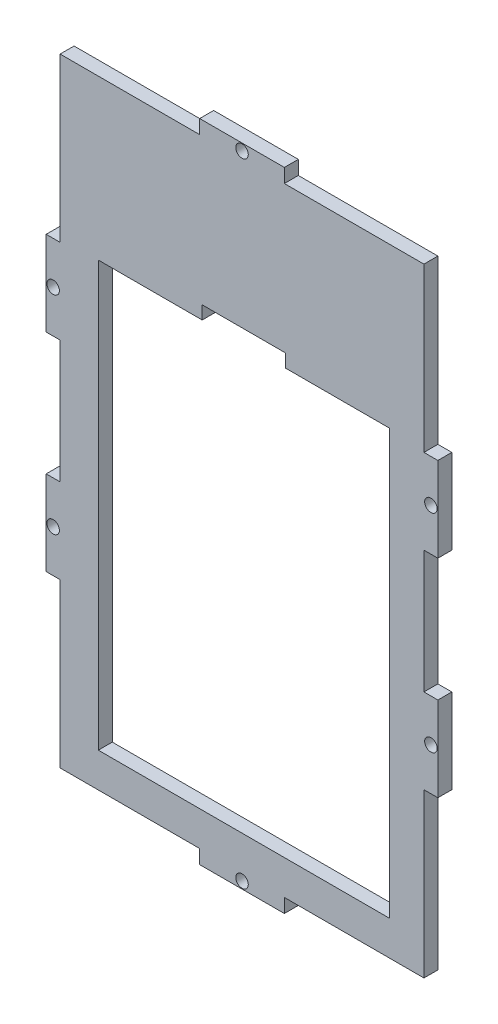
SolidWorks part; units mm, degrees
ref_plane "Front Plane" through (0, 0, 0) normal (0, 0, 1) x (1, 0, 0)
ref_plane "Top Plane" through (0, 0, 0) normal (0, 1, 0) x (1, 0, 0)
ref_plane "Right Plane" through (0, 0, 0) normal (1, 0, 0) x (0, 0, -1)
sketch "Sketch1" plane through (0, 0, 0) normal (0, 0, 1) x (1, 0, 0)
  line L0 (-41.465, 70.465) -> (-13.8217, 70.465)
  line L1 (-41.465, -70.465) -> (41.465, -70.465)
  line L2 (-41.465, -70.465) -> (-41.465, 70.465)
  line L3 (-41.465, 70.465) -> (41.465, 70.465) construction
  line L4 (41.465, -70.465) -> (41.465, 70.465)
  line L5 (-41.465, -70.465) -> (41.465, 70.465) construction
  line L6 (-41.465, 70.465) -> (41.465, -70.465) construction
  line L7 (-13.8217, 70.465) -> (13.8217, 70.465)
  line L8 (13.8217, 70.465) -> (41.465, 70.465)
  point P0 (0, 0)
  dimension "D1" = 82.93
  dimension "D2" = 140.93
extrude "Boss-Extrude1" add sketch "Sketch1" along normal blind 3.18
sketch "Sketch3" plane through (0, 0, 0) normal (0, 0, -1) x (-1, 0, 0)
  line L0 (-33.5967, 34.1533) -> (-33.5967, -62.5967)
  line L1 (-33.5967, -62.5967) -> (32.7533, -62.5967)
  line L2 (32.7533, -62.5967) -> (32.7533, 34.1533)
  line L3 (32.7533, 34.1533) -> (9.0783, 34.1533)
  line L4 (9.0783, 34.1533) -> (9.0783, 37.1533)
  line L5 (9.0783, 37.1533) -> (-9.9217, 37.1533)
  line L6 (-9.9217, 37.1533) -> (-9.9217, 34.1533)
  line L7 (-9.9217, 34.1533) -> (-33.5967, 34.1533)
  line L8 (32.7533, 43.1533) -> (-33.5967, 43.1533)
  line L9 (32.7533, -62.5967) -> (32.7533, 43.1533)
  line L10 (-33.5967, -62.5967) -> (32.7533, -62.5967)
  line L11 (-33.5967, 43.1533) -> (-33.5967, -62.5967)
  line L12 (-33.5967, -62.5967) -> (-33.5967, -70.465) construction
  line L13 (41.465, -70.465) -> (-41.465, -70.465) construction
  line L14 (-33.5967, -62.5967) -> (-41.465, -62.5967) construction
  line L15 (-41.465, -70.465) -> (-41.465, 70.465) construction
  dimension "D1" = 66.35
  dimension "D2" = 96.75
  dimension "D3" = 105.75
  dimension "D4" = 19
  dimension "D5" = 3
extrude "Cut-Extrude1" cut sketch "Sketch3" against normal through all contours L6 L7 L0 L1 L2 L3 L4 L5 region at (0.4217, -13.7828, 0)
sketch "Sketch4" plane through (-41.465, 0, 0) normal (-1, 0, 0) x (0, 0, 1)
  line L0 (1.59, -70.465) -> (1.59, -23.645) construction
  line L1 (3.18, -70.465) -> (0, -70.465) construction
  line L2 (1.59, 70.465) -> (1.59, 23.645) construction
  line L3 (3.18, 70.465) -> (0, 70.465) construction
  line L4 (3.18, 70.465) -> (3.18, -70.465) construction
  line L5 (0, 33.295) -> (3.18, 33.295)
  line L6 (0, 33.295) -> (0, 13.995)
  line L7 (0, 13.995) -> (3.18, 13.995)
  line L8 (3.18, 33.295) -> (3.18, 13.995)
  line L9 (0, 33.295) -> (3.18, 13.995) construction
  line L10 (0, 13.995) -> (3.18, 33.295) construction
  line L12 (0, -33.295) -> (3.18, -33.295)
  line L13 (0, -33.295) -> (0, -13.995)
  line L14 (0, -13.995) -> (3.18, -13.995)
  line L15 (3.18, -33.295) -> (3.18, -13.995)
  line L16 (0, -33.295) -> (3.18, -13.995) construction
  line L17 (0, -13.995) -> (3.18, -33.295) construction
  dimension "D1" = 19.3
  dimension "D2" = 46.82
  dimension "D3" = 46.82
extrude "Boss-Extrude2" add sketch "Sketch4" along normal blind 3.18
sketch "Sketch5" plane through (0, 0, 3.18) normal (0, 0, 1) x (1, 0, 0)
  line L0 (-43.055, 33.295) -> (-43.055, 13.995) construction
  line L1 (-44.645, 33.295) -> (-41.465, 33.295) construction
  line L2 (-44.645, 13.995) -> (-41.465, 13.995) construction
  line L3 (-43.055, -13.995) -> (-43.055, -33.295) construction
  line L4 (-44.645, -13.995) -> (-41.465, -13.995) construction
  line L5 (-44.645, -33.295) -> (-41.465, -33.295) construction
  circle A0 centre (-43.055, 23.645) radius 1.425
  circle A1 centre (-43.055, -23.645) radius 1.425
extrude "Cut-Extrude2" cut sketch "Sketch5" against normal through all
sketch "Sketch6" plane through (41.465, 0, 0) normal (1, 0, 0) x (0, 0, -1)
  line L0 (-1.59, 70.465) -> (-1.59, 23.645) construction
  line L1 (-3.18, 70.465) -> (0, 70.465) construction
  line L2 (-1.59, -70.465) -> (-1.59, -23.645) construction
  line L3 (-3.18, -70.465) -> (0, -70.465) construction
  line L4 (0, -70.465) -> (0, 70.465) construction
  line L5 (-3.18, -33.295) -> (0, -33.295)
  line L6 (-3.18, -33.295) -> (-3.18, -13.995)
  line L7 (-3.18, -13.995) -> (0, -13.995)
  line L8 (0, -33.295) -> (0, -13.995)
  line L9 (-3.18, -33.295) -> (0, -13.995) construction
  line L10 (-3.18, -13.995) -> (0, -33.295) construction
  line L12 (-3.18, 33.295) -> (0, 33.295)
  line L13 (-3.18, 33.295) -> (-3.18, 13.995)
  line L14 (-3.18, 13.995) -> (0, 13.995)
  line L15 (0, 33.295) -> (0, 13.995)
  line L16 (-3.18, 33.295) -> (0, 13.995) construction
  line L17 (-3.18, 13.995) -> (0, 33.295) construction
  dimension "D1" = 19.3
  dimension "D2" = 46.82
  dimension "D3" = 46.82
extrude "Boss-Extrude3" add sketch "Sketch6" along normal blind 3.18
sketch "Sketch7" plane through (0, 0, 3.18) normal (0, 0, 1) x (1, 0, 0)
  line L0 (43.055, 33.295) -> (43.055, 13.995) construction
  line L1 (44.645, 33.295) -> (41.465, 33.295) construction
  line L2 (44.645, 13.995) -> (41.465, 13.995) construction
  line L3 (43.055, -13.995) -> (43.055, -33.295) construction
  line L4 (44.645, -13.995) -> (41.465, -13.995) construction
  line L5 (44.645, -33.295) -> (41.465, -33.295) construction
  circle A0 centre (43.055, 23.645) radius 1.425
  circle A1 centre (43.055, -23.645) radius 1.425
extrude "Cut-Extrude3" cut sketch "Sketch7" against normal through all
sketch "Sketch9" plane through (-41.465, 0, 0) normal (-1, 0, 0) x (0, 0, 1)
  line L0 (0, 51.88) -> (3.18, 51.88) construction
  line L1 (0, 70.465) -> (0, 33.295) construction
  line L2 (3.18, 70.465) -> (3.18, 33.295) construction
  line L4 (0, 42.23) -> (3.18, 42.23)
  line L5 (0, 42.23) -> (0, 61.53)
  line L6 (0, 61.53) -> (3.18, 61.53)
  line L7 (3.18, 42.23) -> (3.18, 61.53)
  line L8 (0, 42.23) -> (3.18, 61.53) construction
  line L9 (0, 61.53) -> (3.18, 42.23) construction
  point P6 (1.59, 51.88)
  dimension "D1" = 19.3
extrude "Boss-Extrude4" [suppressed] add sketch "Sketch9" along normal blind 3.18
sketch "Sketch10" [suppressed] plane through (0, 0, 3.18) normal (0, 0, 1) x (1, 0, 0)
  line L0 (-43.055, 9.65) -> (-43.055, -9.65) construction
  line L1 (-44.645, 9.65) -> (-41.465, 9.65) construction
  line L2 (-44.645, -9.65) -> (-41.465, -9.65) construction
  circle A0 centre (-43.055, 0) radius 1.425
extrude "Cut-Extrude4" [suppressed] cut sketch "Sketch10" against normal through all
mirror "Mirror1" [suppressed] about plane through (0, 0, 0) normal (1, 0, 0)
sketch "Sketch13" plane through (0, 70.465, 0) normal (0, 1, 0) x (1, 0, 0)
  line L0 (0, 0) -> (0, -3.18) construction
  line L1 (41.465, -3.18) -> (-41.465, -3.18) construction
  line L3 (-9.65, -3.18) -> (9.65, -3.18)
  line L4 (-9.65, -3.18) -> (-9.65, 0)
  line L5 (-9.65, 0) -> (9.65, 0)
  line L6 (9.65, -3.18) -> (9.65, 0)
  line L7 (-9.65, -3.18) -> (9.65, 0) construction
  line L8 (-9.65, 0) -> (9.65, -3.18) construction
  point P5 (0, -1.59)
  dimension "D1" = 19.3
extrude "Boss-Extrude6" add sketch "Sketch13" along normal blind 3.18
sketch "Sketch14" plane through (0, 0, 3.18) normal (0, 0, 1) x (1, 0, 0)
  line L0 (-9.65, 72.055) -> (9.65, 72.055) construction
  line L1 (-9.65, 73.645) -> (-9.65, 70.465) construction
  line L2 (9.65, 73.645) -> (9.65, 70.465) construction
  circle A0 centre (0, 72.055) radius 1.425
extrude "Cut-Extrude6" cut sketch "Sketch14" against normal through all
sketch "Sketch15" plane through (0, -70.465, 0) normal (0, -1, 0) x (1, 0, 0)
  line L0 (0, 0) -> (0, 3.18) construction
  line L1 (-41.465, 0) -> (41.465, 0) construction
  line L2 (-41.465, 3.18) -> (41.465, 3.18) construction
  line L4 (-9.65, 3.18) -> (9.65, 3.18)
  line L5 (-9.65, 3.18) -> (-9.65, 0)
  line L6 (-9.65, 0) -> (9.65, 0)
  line L7 (9.65, 3.18) -> (9.65, 0)
  line L8 (-9.65, 3.18) -> (9.65, 0) construction
  line L9 (-9.65, 0) -> (9.65, 3.18) construction
  point P6 (0, 1.59)
  dimension "D1" = 19.3
extrude "Boss-Extrude7" add sketch "Sketch15" along normal blind 3.18
sketch "Sketch16" plane through (0, 0, 3.18) normal (0, 0, 1) x (1, 0, 0)
  line L0 (-9.65, -72.055) -> (9.65, -72.055) construction
  line L1 (-9.65, -73.645) -> (-9.65, -70.465) construction
  line L2 (9.65, -73.645) -> (9.65, -70.465) construction
  circle A0 centre (0, -72.055) radius 1.425
extrude "Cut-Extrude7" cut sketch "Sketch16" against normal through all
sketch "Sketch18" plane through (41.465, 0, 0) normal (1, 0, 0) x (0, 0, -1)
  line L0 (0, -51.88) -> (-3.18, -51.88) construction
  line L1 (0, -70.465) -> (0, -33.295) construction
  line L2 (-3.18, -70.465) -> (-3.18, -33.295) construction
  line L4 (-3.18, -61.53) -> (0, -61.53)
  line L5 (-3.18, -61.53) -> (-3.18, -42.23)
  line L6 (-3.18, -42.23) -> (0, -42.23)
  line L7 (0, -61.53) -> (0, -42.23)
  line L8 (-3.18, -61.53) -> (0, -42.23) construction
  line L9 (-3.18, -42.23) -> (0, -61.53) construction
  point P6 (-1.59, -51.88)
  dimension "D1" = 19.3
extrude "Boss-Extrude8" [suppressed] add sketch "Sketch18" along normal blind 3.18
sketch "Sketch19" [suppressed] plane through (0, 0, 3.18) normal (0, 0, 1) x (1, 0, 0)
  line L0 (43.055, -9.65) -> (43.055, 9.65) construction
  line L1 (44.645, -9.65) -> (41.465, -9.65) construction
  line L2 (44.645, 9.65) -> (41.465, 9.65) construction
  circle A0 centre (43.055, 0) radius 1.425
extrude "Cut-Extrude8" [suppressed] cut sketch "Sketch19" against normal through all
mirror "Mirror2" [suppressed] about plane through (0, 0, 0) normal (1, 0, 0)
sketch "Sketch20" plane through (0, 0, 3.18) normal (0, 0, 1) x (1, 0, 0)
  line L0 (0, 70.465) -> (0, 0) construction
  line L1 (41.465, 70.465) -> (9.65, 70.465) construction
  line L2 (-9.65, 70.465) -> (9.65, 70.465)
  line L3 (9.65, 70.465) -> (9.65, 67.285)
  line L4 (9.65, 67.285) -> (1.425, 67.285)
  line L5 (1.425, 67.285) -> (1.425, 59.485)
  line L6 (1.425, 59.485) -> (3.175, 59.485)
  line L7 (3.175, 59.485) -> (3.175, 57.105)
  line L8 (3.175, 57.105) -> (1.425, 57.105)
  line L9 (1.425, 57.105) -> (1.425, 51.485)
  line L10 (1.425, 51.485) -> (-1.425, 51.485)
  line L11 (-1.425, 51.485) -> (-1.425, 57.105)
  line L12 (-1.425, 57.105) -> (-3.175, 57.105)
  line L13 (-3.175, 57.105) -> (-3.175, 59.485)
  line L14 (-3.175, 59.485) -> (-1.425, 59.485)
  line L15 (-1.425, 59.485) -> (-1.425, 67.285)
  line L16 (-1.425, 67.285) -> (-9.65, 67.285)
  line L17 (-9.65, 67.285) -> (-9.65, 70.465)
  dimension "D1" = 19.3
  dimension "D2" = 3.18
  dimension "D3" = 15.8
  dimension "D4" = 6.35
  dimension "D5" = 2.38
  dimension "D6" = 2.85
  dimension "D7" = 7.8
extrude "Cut-Extrude9" [suppressed] cut sketch "Sketch20" against normal through all
mirror "Mirror3" [suppressed] about plane through (0, 0, 0) normal (0, 1, 0)
sketch "Sketch23" plane through (0, 0, 3.18) normal (0, 0, 1) x (1, 0, 0)
  line L0 (-41.465, 10.815) -> (-41.465, 30.115)
  line L1 (-41.465, 70.465) -> (-41.465, 33.295) construction
  line L2 (-41.465, 30.115) -> (-38.285, 30.115)
  line L3 (-38.285, 30.115) -> (-38.285, 21.89)
  line L4 (-38.285, 21.89) -> (-30.485, 21.89)
  line L5 (-30.485, 21.89) -> (-31.5806, 23.4685)
  line L6 (-31.5806, 23.4685) -> (-29.2006, 23.4685)
  line L7 (-29.2006, 23.4685) -> (-28.105, 21.89)
  line L8 (-28.105, 21.89) -> (-22.485, 21.89)
  line L9 (-22.485, 21.89) -> (-22.485, 19.04)
  line L10 (-22.485, 19.04) -> (-28.105, 19.04)
  line L11 (-28.105, 19.04) -> (-28.105, 17.1185)
  line L12 (-28.105, 17.1185) -> (-30.485, 17.1185)
  line L13 (-30.485, 17.1185) -> (-30.485, 19.04)
  line L14 (-30.485, 19.04) -> (-38.285, 19.04)
  line L15 (-38.285, 19.04) -> (-38.285, 10.815)
  line L16 (-38.285, 10.815) -> (-41.465, 10.815)
  line L17 (-9.65, 70.465) -> (-41.465, 70.465) construction
  line L19 (-22.485, 20.465) -> (-41.465, 20.465) construction
  line L20 (-41.465, -30.115) -> (-41.465, -10.815)
  line L21 (-41.465, -10.815) -> (-38.285, -10.815)
  line L22 (-38.285, -10.815) -> (-38.285, -19.04)
  line L23 (-38.285, -19.04) -> (-30.485, -19.04)
  line L24 (-30.485, -19.04) -> (-30.485, -17.29)
  line L25 (-30.485, -17.29) -> (-28.105, -17.29)
  line L26 (-28.105, -17.29) -> (-28.105, -19.04)
  line L27 (-28.105, -19.04) -> (-22.485, -19.04)
  line L28 (-22.485, -19.04) -> (-22.485, -21.89)
  line L29 (-22.485, -21.89) -> (-28.105, -21.89)
  line L30 (-28.105, -21.89) -> (-28.105, -23.64)
  line L31 (-28.105, -23.64) -> (-30.485, -23.64)
  line L32 (-30.485, -23.64) -> (-30.485, -21.89)
  line L33 (-30.485, -21.89) -> (-38.285, -21.89)
  line L34 (-38.285, -21.89) -> (-38.285, -30.115)
  line L35 (-38.285, -30.115) -> (-41.465, -30.115)
  line L36 (-41.465, -20.465) -> (-22.485, -20.465) construction
  line L37 (-41.465, -70.465) -> (-9.65, -70.465) construction
  dimension "D1" = 50
  dimension "D2" = 19.3
  dimension "D3" = 3.18
  dimension "D4" = 15.8
  dimension "D5" = 6.35
  dimension "D6" = 2.85
  dimension "D7" = 7.8
  dimension "D8" = 2.38
  dimension "D9" = 19.3
  dimension "D10" = 3.18
  dimension "D11" = 7.8
  dimension "D12" = 15.8
  dimension "D13" = 6.35
  dimension "D14" = 2.85
  dimension "D15" = 2.38
  dimension "D16" = 50
extrude "Cut-Extrude10" [suppressed] cut sketch "Sketch23" against normal through all
